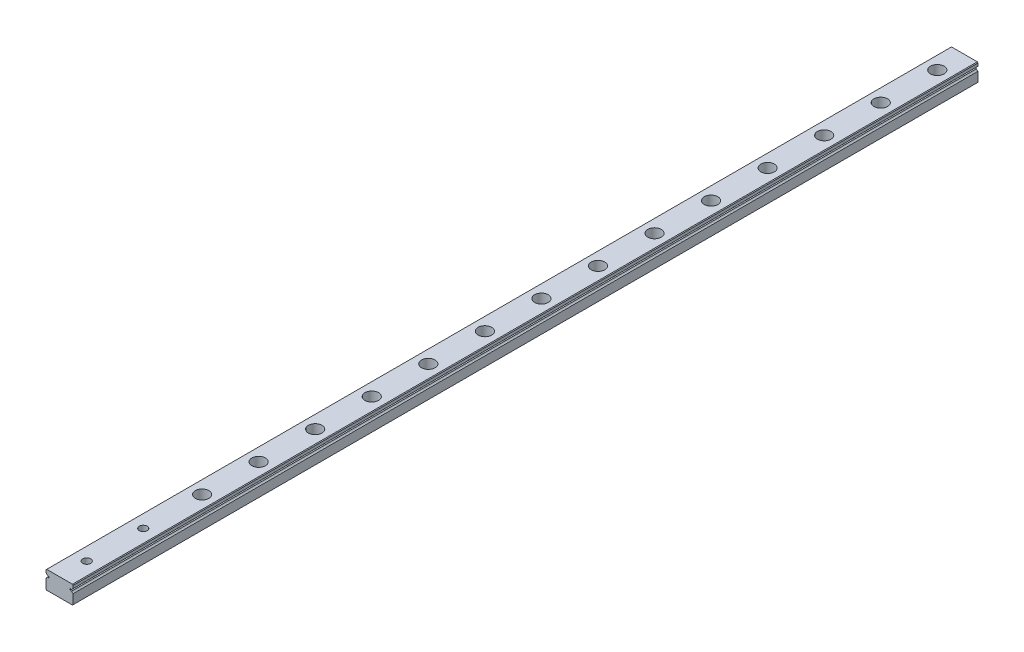
SolidWorks part; units mm, degrees
ref_plane "Спереди" through (0, 0, 0) normal (0, 0, 1) x (1, 0, 0)
ref_plane "Сверху" through (0, 0, 0) normal (0, 1, 0) x (1, 0, 0)
ref_plane "Справа" through (0, 0, 0) normal (1, 0, 0) x (0, 0, -1)
sketch "Эскиз1" plane through (0, 0, 0) normal (0, 0, 1) x (1, 0, 0)
  line L0 (-6, 3.7) -> (-5.7, 4)
  line L1 (-5.7, -4) -> (5.7, -4)
  line L2 (-6, -3.7) -> (-6, 0.549)
  line L3 (-5.7, 4) -> (5.7, 4)
  line L4 (6, -3.7) -> (6, 0.549)
  line L5 (-6, -4) -> (6, 4) construction
  line L6 (-6, 4) -> (6, -4) construction
  line L7 (-6, -3.7) -> (-5.7, -4)
  line L8 (5.7, -4) -> (6, -3.7)
  line L9 (5.7, 4) -> (6, 3.7)
  line L10 (-6, 2.451) -> (-6, 3.7)
  line L11 (-5.3546, 1.7981) -> (-4.6435, 1.7981)
  line L12 (0, 5.4188) -> (0, -5.747) construction
  line L13 (-5.3546, 1.2019) -> (-4.6435, 1.2019)
  line L14 (-4.6435, 1.7981) -> (-4.6435, 1.2019)
  line L15 (4.6435, 1.7981) -> (4.6435, 1.2019)
  line L16 (5.3546, 1.2019) -> (4.6435, 1.2019)
  line L17 (5.3546, 1.7981) -> (4.6435, 1.7981)
  line L18 (6, 2.451) -> (6, 3.7)
  line L19 (4.6435, 1.7981) -> (5.3546, 1.7981) construction
  arc A0 (-6, 0.549) -> (-5.3546, 1.2019) centre (-6.3091, 1.5) ccw
  arc A1 (-5.3546, 1.7981) -> (-6, 2.451) centre (-6.3091, 1.5) ccw
  arc A2 (5.3546, 1.7981) -> (6, 2.451) centre (6.3091, 1.5) cw
  arc A3 (6, 0.549) -> (5.3546, 1.2019) centre (6.3091, 1.5) cw
  point P0 (0, 0)
extrude "Бобышка-Вытянуть1" add sketch "Эскиз1" along normal blind 400
sketch "Эскиз2" plane through (0, 4, 0) normal (0, 1, 0) x (1, 0, 0)
  line L0 (0, 0) -> (0, -26.2396) construction
  line L1 (5.7, 0) -> (-5.7, 0) construction
  line L2 (-3.8306, -12) -> (3.8306, -12) construction
  circle A0 centre (0, -12) radius 3
  circle A1 centre (0, -12) radius 1.75
  dimension "D2" = 3.5
  dimension "D3" = 6
  dimension "D1" = 12
extrude "Вырез-Вытянуть1" cut sketch "Эскиз2" against normal blind 4.5
extrude "Вырез-Вытянуть2" cut sketch "Эскиз2<2>" against normal through all contours A1 region at (0, 4, 12)
sketch "Эскиз2<2>" plane through (0, 4, 0) normal (0, 1, 0) x (1, 0, 0) same geometry as "Эскиз2"
pattern_linear "Линейный массив1" count 14 spacing 25 along (0, 0, 1) of "Вырез-Вытянуть1", "Вырез-Вытянуть2"
sketch "Croquis1" plane through (0, 4, 0) normal (0, 1, 0) x (1, 0, 0)
  line L0 (0, -400) -> (0, -337) construction
  line L1 (5.7, -400) -> (-5.7, -400) construction
  circle A0 centre (0, -388) radius 1.75
  circle A1 centre (0, -363) radius 1.75
  dimension "D1" = 3.5
  dimension "D2" = 3.5
  dimension "D3" = 12
  dimension "D4" = 25
extrude "Cortar-Extruir1" cut sketch "Croquis1" against normal up to surface (8 mm away) up to face at (0, -4, 338.75)
